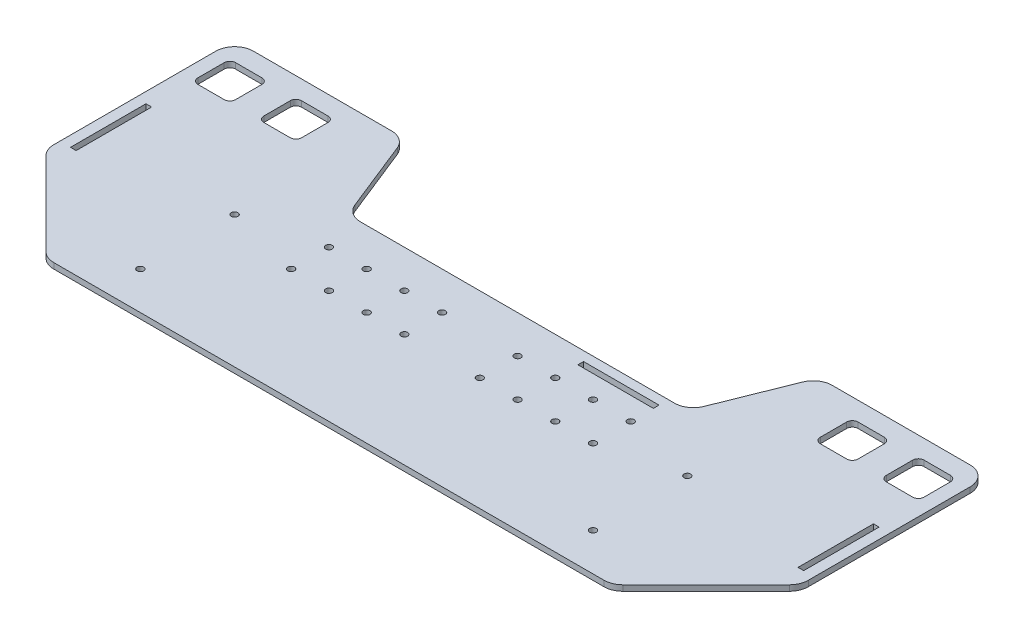
SolidWorks part; units mm, degrees
ref_plane "前视基准面" through (0, 0, 0) normal (0, 0, 1) x (1, 0, 0)
ref_plane "上视基准面" through (0, 0, 0) normal (0, 1, 0) x (1, 0, 0)
ref_plane "右视基准面" through (0, 0, 0) normal (1, 0, 0) x (0, 0, -1)
other "Configuration Table"
sketch "草图1" plane through (0, 0, 0) normal (0, 1, 0) x (1, 0, 0)
  line L0 (-197.0711, -27.9289) -> (-152.9289, -72.0711)
  line L1 (-145.8579, -75) -> (145.8579, -75)
  line L2 (-200, -20.8579) -> (-200, 65)
  line L3 (-190, 75) -> (-116.7703, 75)
  line L4 (200, -20.8579) -> (200, 65)
  line L5 (-200, -75) -> (200, 75) construction
  line L6 (-200, 75) -> (200, -75) construction
  line L7 (152.9289, -72.0711) -> (197.0711, -27.9289)
  line L8 (0, 0) -> (0, 50000) construction
  line L9 (-107.4856, 68.7139) -> (-92.5144, 31.2861)
  line L10 (-83.2297, 25) -> (83.2297, 25)
  line L11 (107.4856, 68.7139) -> (92.5144, 31.2861)
  line L12 (116.7703, 75) -> (190, 75)
  arc A0 (107.4856, 68.7139) -> (116.7703, 75) centre (116.7703, 65) cw
  arc A1 (92.5144, 31.2861) -> (83.2297, 25) centre (83.2297, 35) cw
  arc A2 (-92.5144, 31.2861) -> (-83.2297, 25) centre (-83.2297, 35) ccw
  arc A3 (-107.4856, 68.7139) -> (-116.7703, 75) centre (-116.7703, 65) ccw
  arc A4 (190, 75) -> (200, 65) centre (190, 65) cw
  arc A5 (-200, 65) -> (-190, 75) centre (-190, 65) cw
  arc A6 (197.0711, -27.9289) -> (200, -20.8579) centre (190, -20.8579) ccw
  arc A7 (152.9289, -72.0711) -> (145.8579, -75) centre (145.8579, -65) cw
  arc A8 (-197.0711, -27.9289) -> (-200, -20.8579) centre (-190, -20.8579) cw
  arc A9 (-152.9289, -72.0711) -> (-145.8579, -75) centre (-145.8579, -65) ccw
  point P0 (0, 0)
  point P17 (0, 25)
  point P19 (110, 75)
  point P22 (90, 25)
  point P25 (-90, 25)
  point P28 (-110, 75)
  point P37 (200, -25)
  point P40 (150, -75)
  point P43 (-200, -25)
  point P46 (-150, -75)
  dimension "D8" = 10
  dimension "D9" = 10
  dimension "D1" = 400
  dimension "D2" = 150
  dimension "D3" = 180
  dimension "D4" = 50
  dimension "D5" = 220
extrude "凸台-拉伸1" add sketch "草图1" along normal blind 3
sketch "草图3" plane through (0, 0, 0) normal (0, -1, 0) x (1, 0, 0)
  line L0 (0, 0) -> (0, 50000) construction
  line L1 (-145.8579, 75) -> (145.8579, 75) construction
  circle A0 centre (-120, 55) radius 1.75
  circle A1 centre (-120, 5) radius 1.75
  circle A2 centre (120, 5) radius 1.75
  circle A3 centre (120, 55) radius 1.75
  dimension "D1" = 3.5
  dimension "D2" = 120
  dimension "D3" = 20
  dimension "D4" = 3.5
  dimension "D5" = 50
extrude "切除-拉伸1" cut sketch "草图3" against normal blind 69
sketch "草图4" plane through (0, 3, 0) normal (0, 1, 0) x (1, 0, 0)
  line L0 (-200, 65) -> (-200, -20.8579) construction
  line L1 (-140.5, 45) -> (-154.5, 45)
  line L2 (-137.5, 48) -> (-137.5, 62)
  line L3 (-140.5, 65) -> (-154.5, 65)
  line L4 (-157.5, 48) -> (-157.5, 62)
  line L5 (-175.5, 45) -> (-189.5, 45)
  line L6 (-172.5, 48) -> (-172.5, 62)
  line L7 (-175.5, 65) -> (-189.5, 65)
  line L8 (-192.5, 48) -> (-192.5, 62)
  line L9 (-116.7703, 75) -> (-190, 75) construction
  line L10 (0, 0) -> (0, 50000) construction
  line L11 (192.5, 48) -> (192.5, 62)
  line L12 (175.5, 65) -> (189.5, 65)
  line L13 (172.5, 48) -> (172.5, 62)
  line L14 (175.5, 45) -> (189.5, 45)
  line L15 (157.5, 48) -> (157.5, 62)
  line L16 (140.5, 65) -> (154.5, 65)
  line L17 (137.5, 48) -> (137.5, 62)
  line L18 (140.5, 45) -> (154.5, 45)
  arc A0 (137.5, 48) -> (140.5, 45) centre (140.5, 48) ccw
  arc A1 (140.5, 65) -> (137.5, 62) centre (140.5, 62) ccw
  arc A2 (157.5, 62) -> (154.5, 65) centre (154.5, 62) ccw
  arc A3 (157.5, 48) -> (154.5, 45) centre (154.5, 48) cw
  arc A4 (172.5, 48) -> (175.5, 45) centre (175.5, 48) ccw
  arc A5 (175.5, 65) -> (172.5, 62) centre (175.5, 62) ccw
  arc A6 (192.5, 62) -> (189.5, 65) centre (189.5, 62) ccw
  arc A7 (192.5, 48) -> (189.5, 45) centre (189.5, 48) cw
  arc A8 (-189.5, 45) -> (-192.5, 48) centre (-189.5, 48) cw
  arc A9 (-172.5, 62) -> (-175.5, 65) centre (-175.5, 62) ccw
  arc A10 (-189.5, 65) -> (-192.5, 62) centre (-189.5, 62) ccw
  arc A11 (-175.5, 45) -> (-172.5, 48) centre (-175.5, 48) ccw
  arc A12 (-154.5, 45) -> (-157.5, 48) centre (-154.5, 48) cw
  arc A13 (-137.5, 62) -> (-140.5, 65) centre (-140.5, 62) ccw
  arc A14 (-154.5, 65) -> (-157.5, 62) centre (-154.5, 62) ccw
  arc A15 (-140.5, 45) -> (-137.5, 48) centre (-140.5, 48) ccw
  point P25 (137.5, 45)
  point P28 (137.5, 65)
  point P31 (157.5, 65)
  point P34 (157.5, 45)
  point P37 (172.5, 45)
  point P40 (172.5, 65)
  point P43 (192.5, 65)
  point P46 (192.5, 45)
  point P49 (-192.5, 45)
  point P52 (-172.5, 65)
  point P55 (-192.5, 65)
  point P58 (-172.5, 45)
  point P61 (-157.5, 45)
  point P64 (-137.5, 65)
  point P67 (-157.5, 65)
  point P70 (-137.5, 45)
  dimension "D11" = 3
  dimension "D1" = 20
  dimension "D2" = 20
  dimension "D3" = 15
  dimension "D4" = 7.5
  dimension "D5" = 20
  dimension "D6" = 20
  dimension "D7" = 10
  dimension "D8" = 20
  dimension "D9" = 20
  dimension "D10" = 10
extrude "切除-拉伸2" cut sketch "草图4" against normal blind 69
sketch "草图5" plane through (0, 0, 0) normal (0, -1, 0) x (1, 0, 0)
  line L0 (194.36, 17.65) -> (194.36, -22.35) construction
  line L1 (191.36, 17.65) -> (194.36, 17.65)
  line L2 (191.36, 17.65) -> (191.36, -22.35)
  line L3 (191.36, -22.35) -> (194.36, -22.35)
  line L4 (194.36, 17.65) -> (194.36, -22.35)
  line L5 (0, 0) -> (0, 50000) construction
  line L6 (-194.36, 17.65) -> (-194.36, -22.35)
  line L7 (-191.36, -22.35) -> (-194.36, -22.35)
  line L8 (-191.36, 17.65) -> (-191.36, -22.35)
  line L9 (-191.36, 17.65) -> (-194.36, 17.65)
  dimension "D1" = 40
extrude "切除-拉伸3" cut sketch "草图5" against normal blind 3
sketch "草图6" plane through (0, 0, 0) normal (0, -1, 0) x (1, 0, 0)
  line L0 (0, 0) -> (0, 50000) construction
  line L1 (83.2297, -25) -> (-83.2297, -25) construction
  circle A0 centre (20, -5) radius 1.75
  circle A1 centre (40, -5) radius 1.75
  circle A2 centre (60, -5) radius 1.75
  circle A3 centre (80, -5) radius 1.75
  circle A4 centre (40, 15) radius 1.75
  circle A5 centre (60, 15) radius 1.75
  circle A6 centre (80, 15) radius 1.75
  circle A7 centre (20, 15) radius 1.75
  circle A8 centre (-20, 15) radius 1.75
  circle A9 centre (-80, 15) radius 1.75
  circle A10 centre (-60, 15) radius 1.75
  circle A11 centre (-40, 15) radius 1.75
  circle A12 centre (-80, -5) radius 1.75
  circle A13 centre (-60, -5) radius 1.75
  circle A14 centre (-40, -5) radius 1.75
  circle A15 centre (-20, -5) radius 1.75
  dimension "D1" = 3.5
  dimension "D2" = 20
  dimension "D3" = 20
  dimension "D4" = 4
  dimension "D5" = 2
extrude "切除-拉伸4" cut sketch "草图6" against normal blind 4
sketch "草图7" plane through (0, 0, 0) normal (0, -1, 0) x (1, 0, 0)
  line L1 (40, -20) -> (80, -20)
  line L2 (40, -20) -> (40, -17)
  line L3 (40, -17) -> (80, -17)
  line L4 (80, -20) -> (80, -17)
extrude "切除-拉伸5" cut sketch "草图7" against normal blind 4
